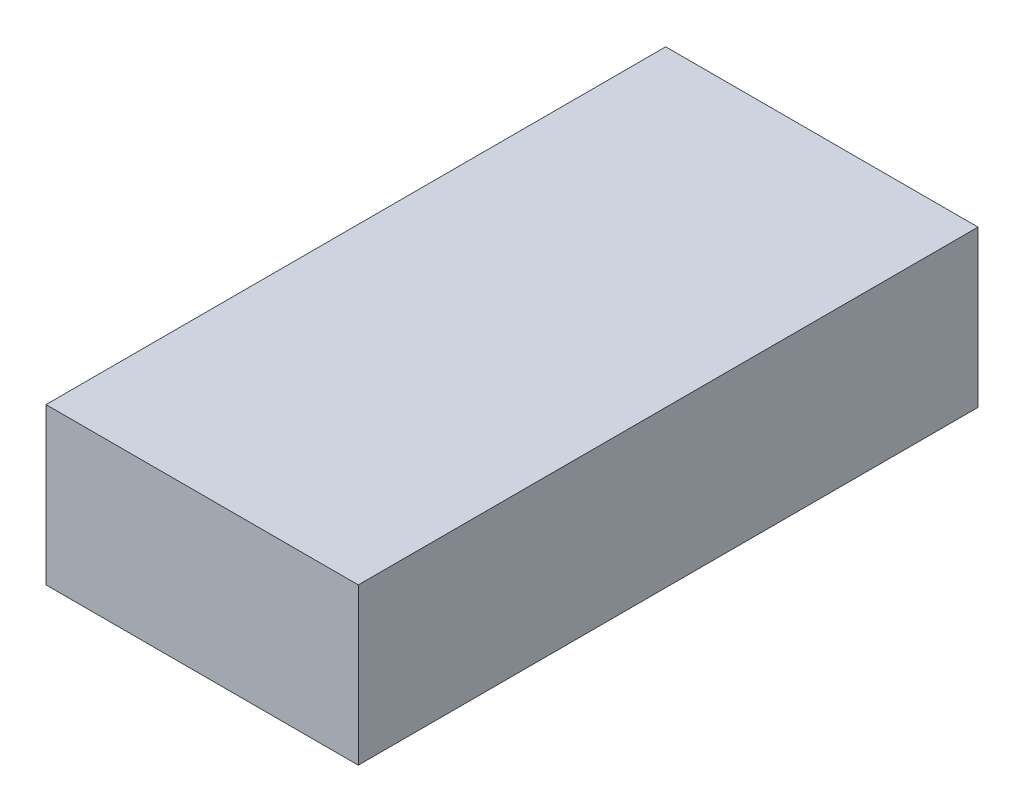
SolidWorks part; units mm, degrees
ref_plane "Front Plane" through (0, 0, 0) normal (0, 0, 1) x (1, 0, 0)
ref_plane "Top Plane" through (0, 0, 0) normal (0, 1, 0) x (1, 0, 0)
ref_plane "Right Plane" through (0, 0, 0) normal (1, 0, 0) x (0, 0, -1)
sketch "Sketch1" plane through (0, 0, 0) normal (0, 0, 1) x (1, 0, 0)
  line L1 (-20, 10) -> (20, 10)
  line L2 (-20, 10) -> (-20, -10)
  line L3 (-20, -10) -> (20, -10)
  line L4 (20, 10) -> (20, -10)
  line L5 (-20, 10) -> (20, -10) construction
  line L6 (-20, -10) -> (20, 10) construction
  point P0 (0, 0)
  point P6 (0, 0)
  dimension "D1" = 20
  dimension "D2" = 40
extrude "Boss-Extrude1" add sketch "Sketch1" along normal blind 39.6875 and the other way blind 39.6875
